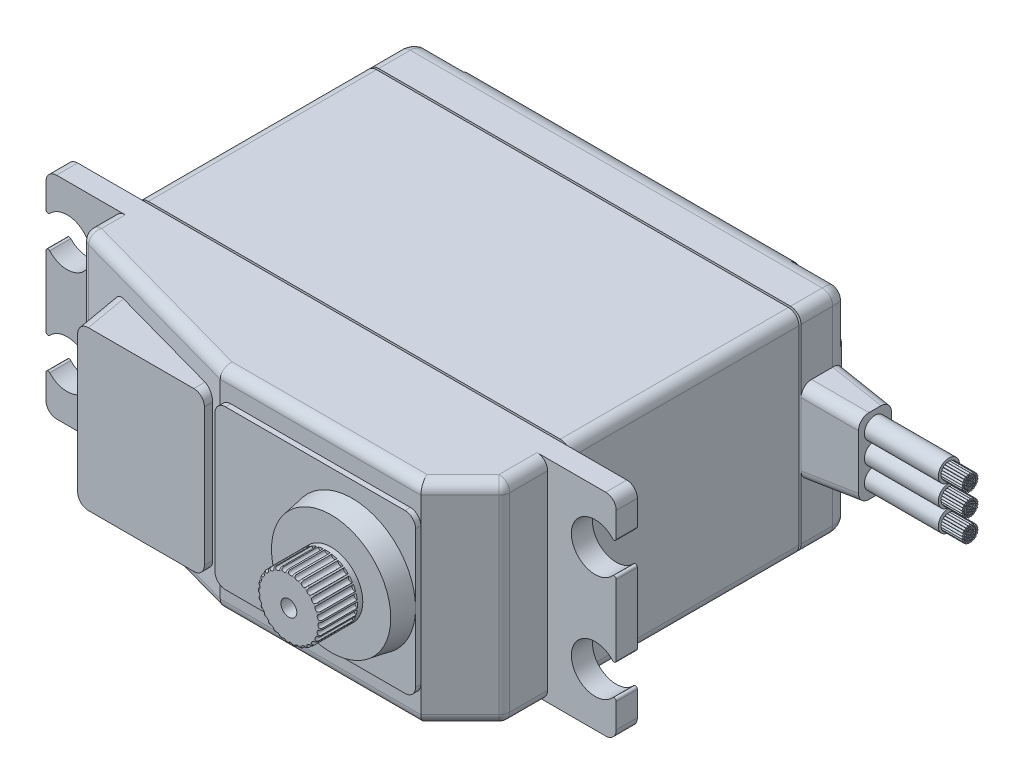
SolidWorks part; units mm, degrees
ref_plane "Plano frontal" through (0, 0, 0) normal (0, 0, 1) x (1, 0, 0)
ref_plane "Plano superior" through (0, 0, 0) normal (0, 1, 0) x (1, 0, 0)
ref_plane "Plano direito" through (0, 0, 0) normal (1, 0, 0) x (0, 0, -1)
sketch "Esboço4" plane through (0, 0, 0) normal (0, 1, 0) x (1, 0, 0)
  line L0 (0, 18.5) -> (0, -18.5) construction
  line L28 (20.5, 18.5) -> (-20.5, 18.5)
  line L29 (-20.5, 18.5) -> (-20.5, -8.5)
  line L30 (-20.5, -8.5) -> (-27, -8.5)
  line L31 (-27, -8.5) -> (-27, -10.5)
  line L32 (-27, -10.5) -> (-20.5, -10.5)
  line L33 (-20.5, -10.5) -> (-20.5, -13.5)
  line L34 (-20.5, -13.5) -> (-2.5, -18.5)
  line L35 (-2.5, -18.5) -> (16.5, -18.5)
  line L36 (16.5, -18.5) -> (20.5, -14.5)
  line L37 (20.5, -14.5) -> (20.5, -10.5)
  line L38 (20.5, -10.5) -> (27, -10.5)
  line L39 (27, -10.5) -> (27, -8.5)
  line L40 (27, -8.5) -> (20.5, -8.5)
  line L41 (20.5, -8.5) -> (20.5, 18.5)
  dimension "D1" = 41
  dimension "D2" = 27
  dimension "D3" = 54
  dimension "D4" = 19
  dimension "D5" = 3
  dimension "D6" = 4
  dimension "D7" = 2
  dimension "D8" = 45
  dimension "D9" = 37
extrude "Ressalto-extrusão4" add sketch "Esboço4" along normal mid plane 20
sketch "Esboço5" plane through (0, 0, 0) normal (0, 1, 0) x (1, 0, 0)
  line L0 (-3.5, -18.2222) -> (-3.5, -19)
  line L1 (-20.5, -13.5) -> (-2.5, -18.5) construction
  line L2 (-3.5, -19) -> (-15.5, -19)
  line L3 (-16.2622, -14.6772) -> (-3.5, -18.2222)
  line L4 (-15.5, -19) -> (-16.2622, -14.6772)
  line L6 (-2.5, -18.5) -> (16.5, -18.5)
  line L7 (-2.5, -18.5) -> (-2.5, -19)
  line L8 (-2.5, -19) -> (16.5, -19)
  line L9 (16.5, -18.5) -> (16.5, -19)
  dimension "D1" = 1
  dimension "D2" = 100
  dimension "D3" = 0.5
  dimension "D4" = 12
extrude "Ressalto-extrusão5" add sketch "Esboço5" along normal mid plane 15
sketch "Esboço6" plane through (20.5, 0, 0) normal (1, 0, 0) x (0, 0, -1)
  line L0 (18.5, 10) -> (18.5, -10) construction
  line L1 (13.5, 4) -> (17.5, 4)
  line L2 (13.5, 4) -> (13.5, -4)
  line L3 (13.5, -4) -> (17.5, -4)
  line L4 (17.5, 4) -> (17.5, -4)
  point P6 (17.5, 0)
  point P7 (18.5, 0)
  dimension "D1" = 1
  dimension "D2" = 8
  dimension "D3" = 4
extrude "Ressalto-extrusão6" add sketch "Esboço6" along normal blind 5 draft 5
sketch "Esboço7" plane through (0, 0, 10.5) normal (0, 0, 1) x (1, 0, 0)
  line L0 (-27, 10) -> (-27, -10) construction
  line L1 (-27, 10) -> (-20.5, 10) construction
  line L2 (-27, 5) -> (-25, 5) construction
  line L3 (-25, 5) -> (-25, 10) construction
  line L4 (-25, -5) -> (-25, -10) construction
  line L5 (-27, -10) -> (-20.5, -10) construction
  line L6 (25, -5) -> (27, -5) construction
  line L7 (27, 10) -> (27, -10) construction
  circle A0 centre (-25, 5) radius 2.25
  circle A1 centre (-25, -5) radius 2.25
  circle A2 centre (25, 5) radius 2.25
  circle A3 centre (25, -5) radius 2.25
  dimension "D1" = 4.5
  dimension "D2" = 2
  dimension "D3" = 10
extrude "Corte-extrusão1" cut sketch "Esboço7" against normal up to surface (2 mm away) up to face at (-23.75, 0, 8.5)
sketch "Esboço8" plane through (0, 0, 19) normal (0, 0, 1) x (1, 0, 0)
  line L0 (-2.5, 0) -> (16.5, 0) construction
  line L1 (-2.5, 7.5) -> (-2.5, -7.5) construction
  line L2 (16.5, 7.5) -> (16.5, -7.5) construction
  line L4 (20.5, 10) -> (20.5, -10) construction
  circle A0 centre (10.5, 0) radius 6
  dimension "D1" = 12
  dimension "D2" = 10
extrude "Ressalto-extrusão7" add sketch "Esboço8" along normal blind 2 draft 10
sketch "Esboço9" plane through (0, 0, 21) normal (0, 0, 1) x (1, 0, 0)
  circle A0 centre (10.5, 0) radius 3
  circle A1 centre (10.5, 0) radius 0.75
  dimension "D1" = 6
  dimension "D2" = 1.5
extrude "Ressalto-extrusão8" add sketch "Esboço9" along normal blind 4
fillet "Filete1" radius 1 28 edges at (-3.5, 7.5, 18.6111) (-3.5, -7.5, 18.6111) (-15.8811, 7.5, 16.8386) (-15.8811, -7.5, 16.8386) (-27, 10, 9.5) (-27, -10, 9.5) (27, 10, 9.5) (27, -10, 9.5) (20.5, 10, 12.5) (20.5, -10, 12.5) (-20.5, 10, 12) (-20.5, -10, 12) (20.5, -10, -5) (-20.5, -10, -5) (20.5, 10, -5) (-20.5, 10, -5) (20.5, 0, 14.5) (-20.5, 0, 13.5) (-11.5, -10, 16) (7, -10, 18.5) (18.5, -10, 16.5) (18.5, 10, 16.5) (-11.5, 10, 16) (7, 10, 18.5)
fillet "Filete2" radius 2 8 edges at (20.2071, 9.7071, -18.5) (20.5, 0, -18.5) (20.2071, -9.7071, -18.5) (0, -10, -18.5) (-20.2071, -9.7071, -18.5) (-20.5, 0, -18.5) (-20.2071, 9.7071, -18.5) (0, 10, -18.5)
sketch "Esboço11" plane through (0, 0, -18.5) normal (0, 0, -1) x (-1, 0, 0)
  line L0 (18.5, 8) -> (-18.5, 8) construction
  line L1 (-18.5, 8) -> (-18.5, -8) construction
  line L2 (-18.5, -8) -> (18.5, -8) construction
  line L3 (18.5, -8) -> (18.5, 8) construction
  line L4 (-17, -5) -> (-20.5, -5)
  line L5 (-20.5, 9) -> (-20.5, -9) construction
  line L6 (-20.5, -5) -> (-20.5, -10)
  line L7 (-26, -10) -> (-19.5, -10) construction
  line L8 (-20.5, -10) -> (-15.5, -10)
  line L9 (19.5, -10) -> (-19.5, -10) construction
  line L10 (-15.5, -10) -> (-15.5, -6.5)
  line L11 (-17, 5) -> (-20.5, 5)
  line L12 (-20.5, 5) -> (-20.5, 10)
  line L13 (-26, 10) -> (-19.5, 10) construction
  line L14 (-20.5, 10) -> (-15.5, 10)
  line L15 (-19.5, 10) -> (19.5, 10) construction
  line L16 (-15.5, 10) -> (-15.5, 6.5)
  line L17 (17, 5) -> (20.5, 5)
  line L18 (20.5, 9) -> (20.5, -9) construction
  line L19 (20.5, 5) -> (20.5, 10)
  line L20 (19.5, 10) -> (26, 10) construction
  line L21 (20.5, 10) -> (15.5, 10)
  line L22 (15.5, 10) -> (15.5, 6.5)
  line L23 (15.5, -6.5) -> (15.5, -10)
  line L24 (15.5, -10) -> (20.5, -10)
  line L25 (19.5, -10) -> (26, -10) construction
  line L26 (20.5, -10) -> (20.5, -5)
  line L27 (20.5, -5) -> (17, -5)
  arc A0 (-17, 5) -> (-15.5, 6.5) centre (-17, 6.5) ccw
  arc A1 (-17, -5) -> (-15.5, -6.5) centre (-17, -6.5) ccw construction
  arc A2 (17, 5) -> (15.5, 6.5) centre (17, 6.5) ccw construction
  arc A3 (17, -5) -> (15.5, -6.5) centre (17, -6.5) ccw
  arc A4 (-15.5, 6.5) -> (-17, 5) centre (-17, 6.5) ccw construction
  arc A5 (-15.5, -6.5) -> (-17, -5) centre (-17, -6.5) ccw
  arc A6 (15.5, 6.5) -> (17, 5) centre (17, 6.5) ccw
  arc A7 (15.5, -6.5) -> (17, -5) centre (17, -6.5) ccw construction
  dimension "D1" = 3
extrude "Corte-extrusão2" cut sketch "Esboço11" against normal blind 1
sketch "Esboço12" plane through (0, 0, -17.5) normal (0, 0, -1) x (-1, 0, 0)
  circle A0 centre (-17, 6.5) radius 0.75
  circle A1 centre (-17, -6.5) radius 0.75
  circle A2 centre (17, -6.5) radius 0.75
  circle A3 centre (17, 6.5) radius 0.75
  dimension "D1" = 1.5
extrude "Corte-extrusão3" cut sketch "Esboço12" against normal blind 5
fillet "Filete3" radius 0.2 8 edges at (-27, -6.0308, 9.5) (-27, 3.9692, 9.5) (27, -6.0308, 9.5) (27, 3.9692, 9.5) (27, -3.9692, 9.5) (27, 6.0308, 9.5) (-27, -3.9692, 9.5) (-27, 6.0308, 9.5)
fillet "Filete4" radius 0.2 1 edges at (13.5, 0, 25)
sketch "Esboço13" plane through (0, 0, 25) normal (0, 0, 1) x (1, 0, 0)
  circle A0 centre (13.5, 0) radius 0.25
  circle A1 centre (10.5, 0) radius 3 construction
  dimension "D1" = 0.5
extrude "Corte-extrusão4" cut sketch "Esboço13" against normal blind 3.5
pattern_circular "PadrãoCircular1" count 29 over 360 about axis through (10.5, 0, 21) along (0, 0, 1) of "Corte-extrusão4"
sketch "Esboço14" plane through (0, 0, 8.5) normal (0, 0, -1) x (-1, 0, 0)
  line L0 (19.5, 10) -> (26, 10) construction
  line L1 (-20.5, -10) -> (20.5, -10)
  line L2 (-20.5, -10) -> (-20.5, 10)
  line L3 (-20.5, 10) -> (20.5, 10)
  line L4 (20.5, -10) -> (20.5, 10)
  line L5 (-20.5, -10) -> (20.5, 10) construction
  line L6 (-20.5, 10) -> (20.5, -10) construction
  line L7 (20.5, 9) -> (20.5, -9) construction
  line L9 (-20, -9.5) -> (20, -9.5)
  line L10 (-20, -9.5) -> (-20, 9.5)
  line L11 (-20, 9.5) -> (20, 9.5)
  line L12 (20, -9.5) -> (20, 9.5)
  line L13 (-20, -9.5) -> (20, 9.5) construction
  line L14 (-20, 9.5) -> (20, -9.5) construction
  point P0 (0, 0)
  point P10 (0, 0)
  dimension "D1" = 0.5
  dimension "D2" = 0.5
extrude "Corte-extrusão5" cut sketch "Esboço14" along normal blind 0.2
ref_plane "Plano1" through (0, 0, -13.5) normal (0, 0, -1) x (-1, 0, 0)
sketch "Esboço15" plane through (0, 0, -13.5) normal (0, 0, -1) x (-1, 0, 0)
  line L4 (-20, -9.5) -> (20, -9.5)
  line L5 (20, -9.5) -> (20, 9.5)
  line L6 (20, 9.5) -> (-20, 9.5)
  line L7 (-20, 9.5) -> (-20, -9.5)
  line L8 (-20, -9.5) -> (20, -9.5)
  line L9 (20, -9.5) -> (20, 9.5)
  line L10 (20, 9.5) -> (-20, 9.5)
  line L11 (-20, 9.5) -> (-20, -9.5)
  line L12 (-20.5, -10) -> (20.5, -10)
  line L13 (20.5, -10) -> (20.5, 10)
  line L14 (20.5, 10) -> (-20.5, 10)
  line L15 (-20.5, 10) -> (-20.5, -10)
  line L16 (-20.5, -10) -> (20.5, -10)
  line L17 (20.5, -10) -> (20.5, 10)
  line L18 (20.5, 10) -> (-20.5, 10)
  line L19 (-20.5, 10) -> (-20.5, -10)
  dimension "D1" = 0
  dimension "D2" = 0
extrude "Corte-extrusão6" cut sketch "Esboço15" against normal blind 0.2
fillet "Filete5" radius 1 4 edges at (22.8588, 3.7936, -17.2936) (22.8588, -3.7936, -17.2936) (23, -3.7813, -13.7187) (23, 3.7813, -13.7187)
sketch "Esboço16" plane through (25.5, 0, 0) normal (1, 0, 0) x (0, 0, -1)
  line L0 (15.5, 2.05) -> (15.5, -2.05) construction
  line L1 (17.0626, 0) -> (13.9374, 0) construction
  line L2 (17.0626, -2.5664) -> (17.0626, 2.5664) construction
  line L3 (13.9374, 2.5664) -> (13.9374, -2.5664) construction
  circle A0 centre (15.5, 2.05) radius 1
  circle A1 centre (15.5, 0) radius 1
  circle A2 centre (15.5, -2.05) radius 1
  dimension "D1" = 2
  dimension "D2" = 4.1
extrude "Ressalto-extrusão9" add sketch "Esboço16" along normal blind 7
sketch "Esboço17" plane through (32.5, 0, 0) normal (1, 0, 0) x (0, 0, -1)
  line L0 (15.5, 2.71) -> (15.5, 2.49) construction
  line L1 (15.5, 2.49) -> (15.5, 2.27) construction
  line L2 (15.5, 2.27) -> (15.5, 2.05) construction
  circle A0 centre (15.5, 2.05) radius 0.1
  circle A1 centre (15.5, 2.27) radius 0.1
  circle A2 centre (15.5, 2.49) radius 0.1
  circle A3 centre (15.5, 2.71) radius 0.1
  circle A4 centre (15.6905, 2.16) radius 0.1
  circle A5 centre (15.6905, 1.94) radius 0.1
  circle A6 centre (15.5, 1.83) radius 0.1
  circle A7 centre (15.3095, 1.94) radius 0.1
  circle A8 centre (15.3095, 2.16) radius 0.1
  circle A9 centre (15.7045, 2.4396) radius 0.1
  circle A10 centre (15.8621, 2.2999) radius 0.1
  circle A11 centre (15.9368, 2.103) radius 0.1
  circle A12 centre (15.9114, 1.894) radius 0.1
  circle A13 centre (15.7918, 1.7207) radius 0.1
  circle A14 centre (15.6053, 1.6228) radius 0.1
  circle A15 centre (15.3947, 1.6228) radius 0.1
  circle A16 centre (15.2082, 1.7207) radius 0.1
  circle A17 centre (15.0886, 1.894) radius 0.1
  circle A18 centre (15.0632, 2.103) radius 0.1
  circle A19 centre (15.1379, 2.2999) radius 0.1
  circle A20 centre (15.2955, 2.4396) radius 0.1
  circle A21 centre (15.7143, 2.6742) radius 0.1
  circle A22 centre (15.9054, 2.5708) radius 0.1
  circle A23 centre (16.0525, 2.411) radius 0.1
  circle A24 centre (16.1398, 2.212) radius 0.1
  circle A25 centre (16.1577, 1.9955) radius 0.1
  circle A26 centre (16.1044, 1.7849) radius 0.1
  circle A27 centre (15.9856, 1.603) radius 0.1
  circle A28 centre (15.8141, 1.4695) radius 0.1
  circle A29 centre (15.6086, 1.399) radius 0.1
  circle A30 centre (15.3914, 1.399) radius 0.1
  circle A31 centre (15.1859, 1.4695) radius 0.1
  circle A32 centre (15.0144, 1.603) radius 0.1
  circle A33 centre (14.8956, 1.7849) radius 0.1
  circle A34 centre (14.8423, 1.9955) radius 0.1
  circle A35 centre (14.8602, 2.212) radius 0.1
  circle A36 centre (14.9475, 2.411) radius 0.1
  circle A37 centre (15.0946, 2.5708) radius 0.1
  circle A38 centre (15.2857, 2.6742) radius 0.1
  point P22 (15.5, 2.05)
  point P47 (15.5, 2.05)
  point P84 (15.5, 2.05)
  dimension "D1" = 0.2
  dimension "D2" = 0.22
  dimension "D3" = 6
  dimension "D4" = 13
  dimension "D5" = 19
extrude "Ressalto-extrusão10" add sketch "Esboço17" along normal blind 2
pattern_linear "Padrão linear1" count 3 spacing 2.1 along (0, -1, 0) of "Ressalto-extrusão10"
